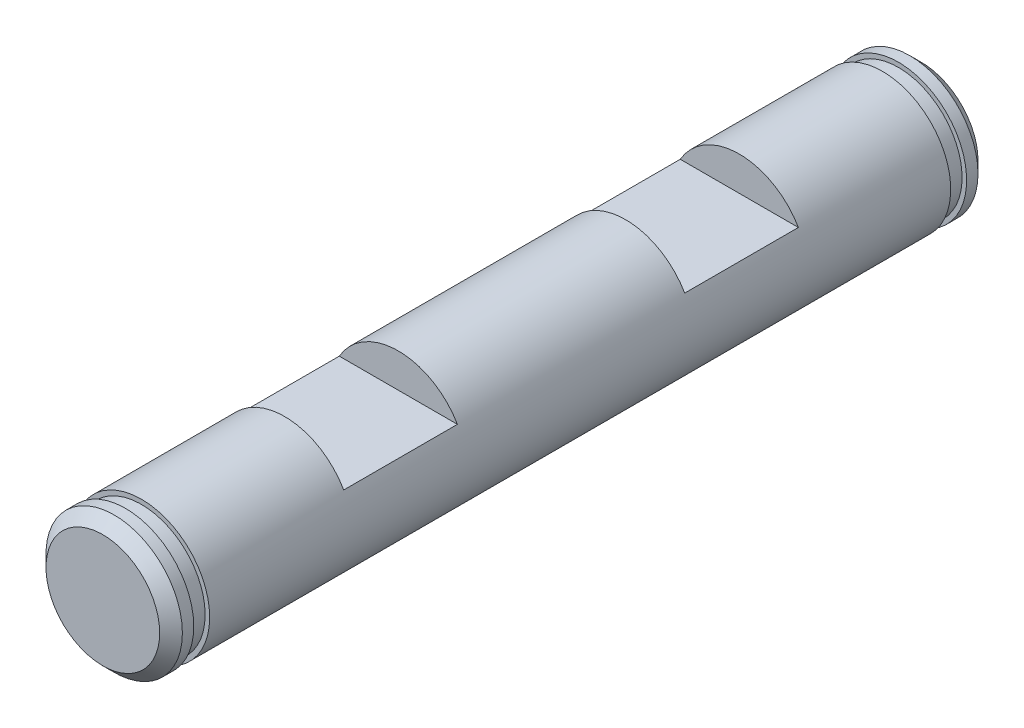
SolidWorks part; units mm, degrees
material "Chromowa stal nierdzewna"
ref_plane "Płaszczyzna przednia" through (0, 0, 0) normal (0, 0, 1) x (1, 0, 0)
ref_plane "Płaszczyzna górna" through (0, 0, 0) normal (0, 1, 0) x (1, 0, 0)
ref_plane "Płaszczyzna prawa" through (0, 0, 0) normal (1, 0, 0) x (0, 0, -1)
sketch "Szkic1" plane through (0, 0, 0) normal (0, 0, 1) x (1, 0, 0)
  circle A0 centre (0, 0) radius 3
  dimension "D1" = 6
extrude "Dodanie-wyciągnięcie1" add sketch "Szkic1" along normal blind 36
chamfer "Sfazowanie1" distance 0.5 angle 45 2 edges at (3, 0, 0) (3, 0, 36)
sketch "Szkic2" plane through (0, 0, 36) normal (0, 0, 1) x (1, 0, 0)
  circle A0 centre (0, 0) radius 3
  circle A1 centre (0, 0) radius 2.8
  dimension "D1" = 6
  dimension "D2" = 5.6
extrude "Wytnij-wyciągnięcie1" cut sketch "Szkic2" against normal blind 0.7 from offset 1 offset against normal yes
sketch "Szkic3" plane through (0, 0, 0) normal (0, 0, -1) x (-1, 0, 0)
  circle A0 centre (0, 0) radius 3
  circle A1 centre (0, 0) radius 2.8
  dimension "D1" = 5.6
  dimension "D2" = 6
extrude "Wytnij-wyciągnięcie2" cut sketch "Szkic3" against normal blind 0.7 from offset 1 offset against normal yes
sketch "Szkic4" plane through (0, 0, 36) normal (0, 0, 1) x (1, 0, 0)
  line L0 (-2.5981, 1.5) -> (2.5981, 1.5)
  arc A0 (2.5981, 1.5) -> (-2.5981, 1.5) centre (0, 0) ccw
  dimension "D1" = 6
  dimension "D2" = 1.5
extrude "Wytnij-wyciągnięcie3" cut sketch "Szkic4" along normal blind 5 from offset 13 offset against normal yes
extrude "Wytnij-wyciągnięcie4" cut sketch "Szkic4<2>" against normal blind 5 from offset 23 offset against normal yes
sketch "Szkic4<2>" plane through (0, 0, 36) normal (0, 0, 1) x (1, 0, 0) same geometry as "Szkic4"
